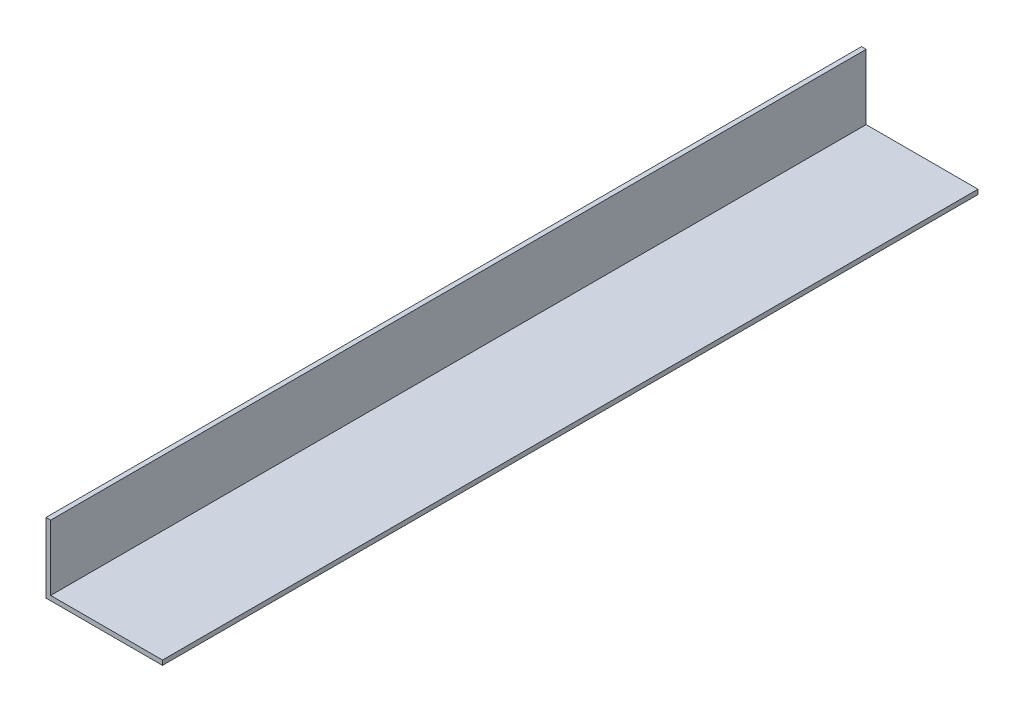
SolidWorks part; units mm, degrees
ref_plane "Front Plane" through (0, 0, 0) normal (0, 0, 1) x (1, 0, 0)
ref_plane "Top Plane" through (0, 0, 0) normal (0, 1, 0) x (1, 0, 0)
ref_plane "Right Plane" through (0, 0, 0) normal (1, 0, 0) x (0, 0, -1)
sketch "Sketch1" plane through (0, 0, 0) normal (0, 0, 1) x (1, 0, 0)
  line L0 (0, 0) -> (0, 30)
  line L1 (0, 30) -> (2, 30)
  line L2 (2, 30) -> (2, 2)
  line L3 (2, 2) -> (50, 2)
  line L4 (50, 2) -> (50, 0)
  line L5 (50, 0) -> (0, 0)
extrude "Boss-Extrude1" add sketch "Sketch1" along normal up to surface (350 mm away)
